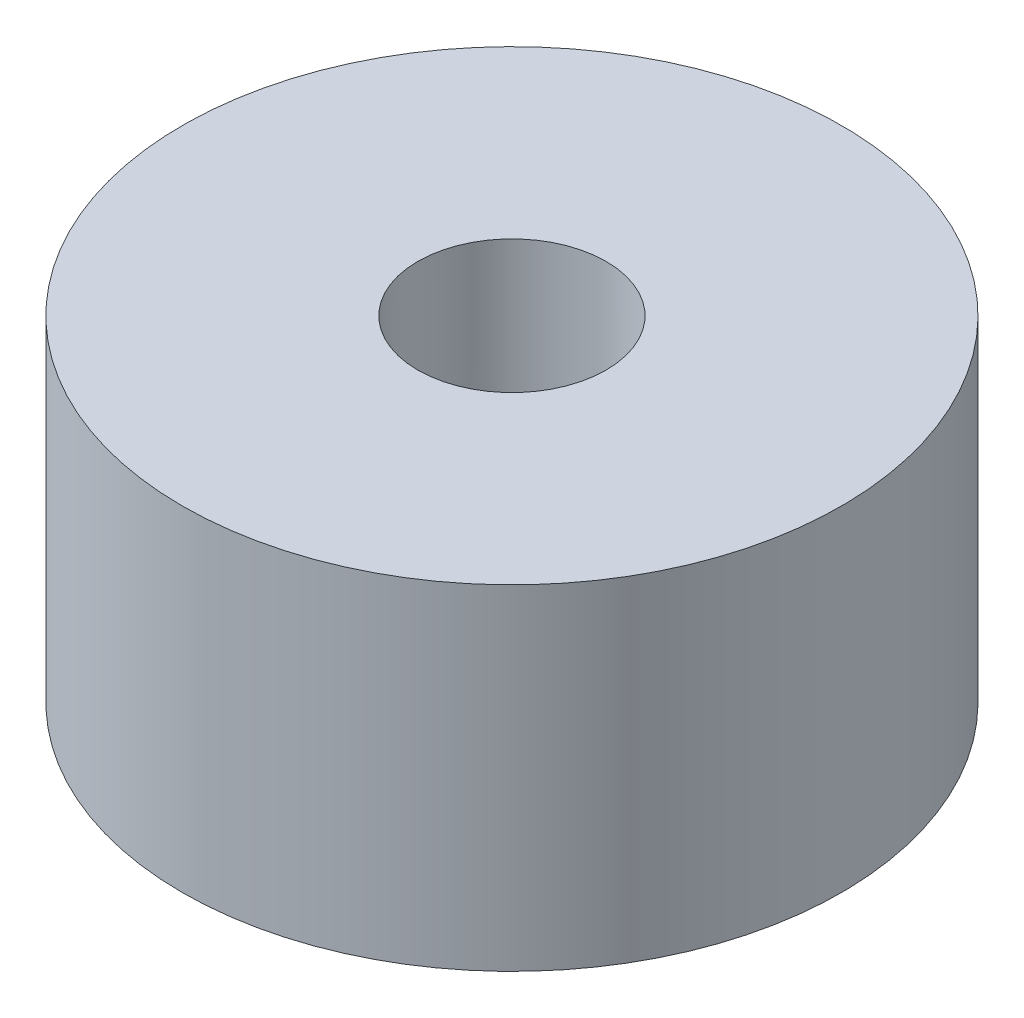
SolidWorks part; units mm, degrees
ref_plane "Front Plane" through (0, 0, 0) normal (0, 0, 1) x (1, 0, 0)
ref_plane "Top Plane" through (0, 0, 0) normal (0, 1, 0) x (1, 0, 0)
ref_plane "Right Plane" through (0, 0, 0) normal (1, 0, 0) x (0, 0, -1)
sketch "Sketch1" plane through (0, 0, 0) normal (0, 1, 0) x (1, 0, 0)
  circle A0 centre (0, 0) radius 7.875
  circle A1 centre (0, 0) radius 2.25
  dimension "D1" = 15.75
  dimension "D2" = 4.5
extrude "Boss-Extrude1" add sketch "Sketch1" along normal blind 8
sketch "Sketch2" plane through (0, 8, 0) normal (0, 1, 0) x (1, 0, 0)
  circle A0 centre (0, 0) radius 4
  circle A1 centre (0, 0) radius 2.25 construction
  dimension "D1" = 8
extrude "Cut-Extrude1" [suppressed] cut sketch "Sketch2" against normal blind 3 draft 45
sketch "Sketch3" plane through (0, 0, 0) normal (0, -1, 0) x (-1, 0, 0)
  circle A0 centre (0, 0) radius 4
  circle A1 centre (0, 0) radius 2.25 construction
  dimension "D1" = 8
extrude "Cut-Extrude2" cut sketch "Sketch3" against normal blind 3
sketch "Sketch4" plane through (0, 3, 0) normal (0, -1, 0) x (1, 0, 0)
  circle A0 centre (0, 0) radius 2.5
  circle A1 centre (0, 0) radius 4
  circle A2 centre (0, 0) radius 4 construction
  dimension "D1" = 5
extrude "Boss-Extrude2" [suppressed] add sketch "Sketch4" along normal blind 2
sketch "Sketch5" [suppressed] plane through (0, 8, 0) normal (0, 1, 0) x (1, 0, 0)
  line L0 (4.437, 6.506) -> (4.437, -6.506)
  line L1 (3.937, -6.9653) -> (3.937, 4.6059) construction
  circle A0 centre (0, 0) radius 7.875 construction
  arc A1 (4.437, -6.506) -> (4.437, 6.506) centre (0, 0) ccw
  dimension "D1" = 0.5
extrude "Boss-Extrude3" [suppressed] add sketch "Sketch5" along normal blind 8
sketch "Sketch6" [suppressed] plane through (3.937, 0, 0) normal (1, 0, 0) x (0, 0, -1)
  line L0 (14.052, 7.7042) -> (-6.463, 7.7042) construction
  line L1 (-6.506, 16) -> (-3.506, 16)
  line L2 (-6.506, 16) -> (-6.506, 7.7042)
  line L3 (-6.506, 7.7042) -> (-3.506, 7.7042)
  line L4 (-3.506, 16) -> (-3.506, 7.7042)
  line L5 (0, 16) -> (0, 7.7042) construction
  line L6 (6.506, 16) -> (-6.506, 16) construction
  line L7 (3.506, 16) -> (3.506, 7.7042)
  line L8 (6.506, 7.7042) -> (3.506, 7.7042)
  line L9 (6.506, 16) -> (6.506, 7.7042)
  line L10 (6.506, 16) -> (3.506, 16)
  dimension "D1" = 3
extrude "Cut-Extrude3" [suppressed] cut sketch "Sketch6" along normal through all
sketch "Sketch7" plane through (0, 8, 0) normal (0, 1, 0) x (1, 0, 0)
  circle A0 centre (0, 0) radius 1.25
  circle A1 centre (0, 0) radius 2.5
  dimension "D1" = 2.5
  dimension "D2" = 5
extrude "Boss-Extrude4" [suppressed] add sketch "Sketch7" along normal blind 10 separate body
sketch "Sketch9" plane through (11.2113, 0, 0) normal (1, 0, 0) x (0, 0, -1)
  circle A0 centre (-6.463, 18.7042) radius 6.35
  circle A1 centre (-6.463, 18.7042) radius 6.35 construction
extrude "Cut-Extrude4" [suppressed] cut sketch "Sketch9" against normal through all
sketch "Sketch10" plane through (6.1024, 0, 0) normal (1, 0, 0) x (0, 0, -1)
  circle A0 centre (8.6773, 18.7042) radius 8.5
  dimension "D1" = 17
extrude "Cut-Extrude5" [suppressed] cut sketch "Sketch10" against normal through all
ref_plane "Plane1" [suppressed] through (2.5, 0, 0) normal (1, 0, 0) x (0, 0, -1)
